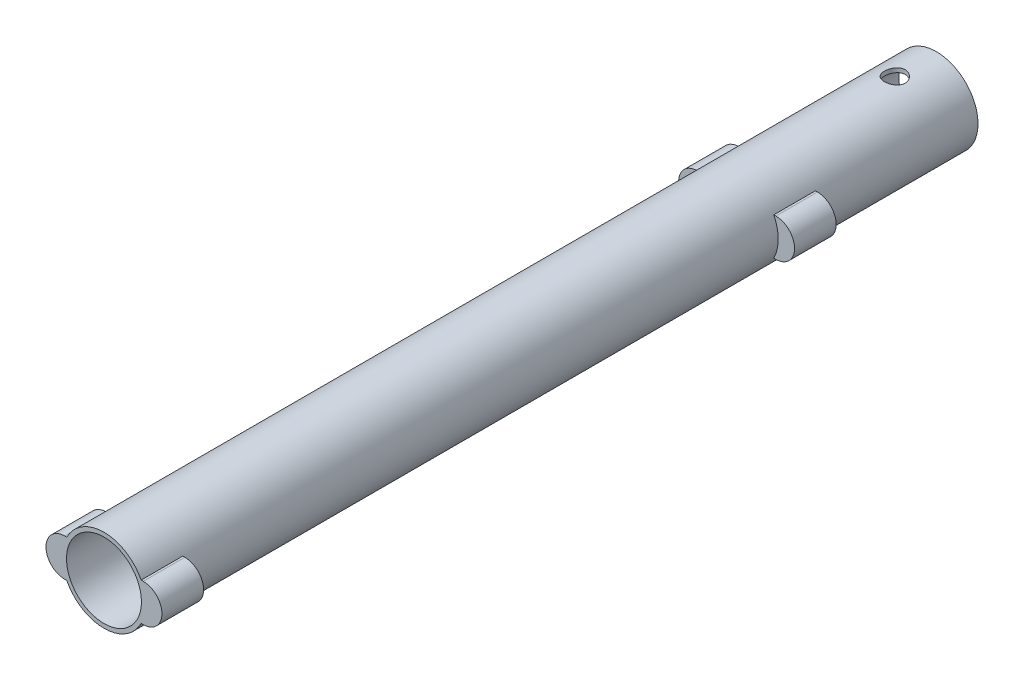
SolidWorks part; units mm, degrees
ref_plane "Front Plane" through (0, 0, 0) normal (0, 0, 1) x (1, 0, 0)
ref_plane "Top Plane" through (0, 0, 0) normal (0, 1, 0) x (1, 0, 0)
ref_plane "Right Plane" through (0, 0, 0) normal (1, 0, 0) x (0, 0, -1)
sketch "Sketch1" plane through (0, 0, 0) normal (0, 0, 1) x (1, 0, 0)
  circle A0 centre (0, 0) radius 10
  circle A1 centre (0, 0) radius 9
  dimension "D1" = 20
  dimension "D2" = 18
extrude "Boss-Extrude1" add sketch "Sketch1" along normal blind 200
sketch "Sketch2" plane through (0, 0, 200) normal (0, 0, 1) x (1, 0, 0)
  line L0 (-9.4303, 0) -> (10.5697, 0) construction
  line L1 (-9.4303, 4.5) -> (-8.9303, 4.5)
  line L2 (-9.4303, -4.5) -> (-8.9303, -4.5)
  line L3 (8.9303, 4.5) -> (9.4303, 4.5)
  line L4 (8.9303, -4.5) -> (9.4303, -4.5)
  arc A0 (-9.4303, 4.5) -> (-9.4303, -4.5) centre (-9.4303, 0) ccw
  circle A2 centre (0, 0) radius 10 construction
  arc A3 (-8.9303, 4.5) -> (-8.9303, -4.5) centre (0, 0) ccw
  arc A4 (8.9303, -4.5) -> (8.9303, 4.5) centre (0, 0) ccw
  arc A6 (9.4303, 4.5) -> (9.4303, -4.5) centre (9.4303, 0) cw
  point P2 (0, 0)
  dimension "D6" = 0.5
  dimension "D1" = 20
  dimension "D2" = 9
  dimension "D3" = 0.5
  dimension "D4" = 0.5
  dimension "D5" = 0.5
extrude "Boss-Extrude2" add sketch "Sketch2" against normal blind 10
ref_plane "Plane1" through (0, 0, 119) normal (0, 0, 1) x (1, 0, 0)
mirror "Mirror1" about plane through (0, 0, 119) normal (0, 0, 1) of "Boss-Extrude2"
sketch "Sketch3" plane through (0, 0, 0) normal (0, 1, 0) x (1, 0, 0)
  circle A0 centre (0, -10) radius 2.5
  point P2 (0, 0)
  dimension "D1" = 5
  dimension "D2" = 10
extrude "Cut-Extrude1" cut sketch "Sketch3" against normal through all both and the other way through all
